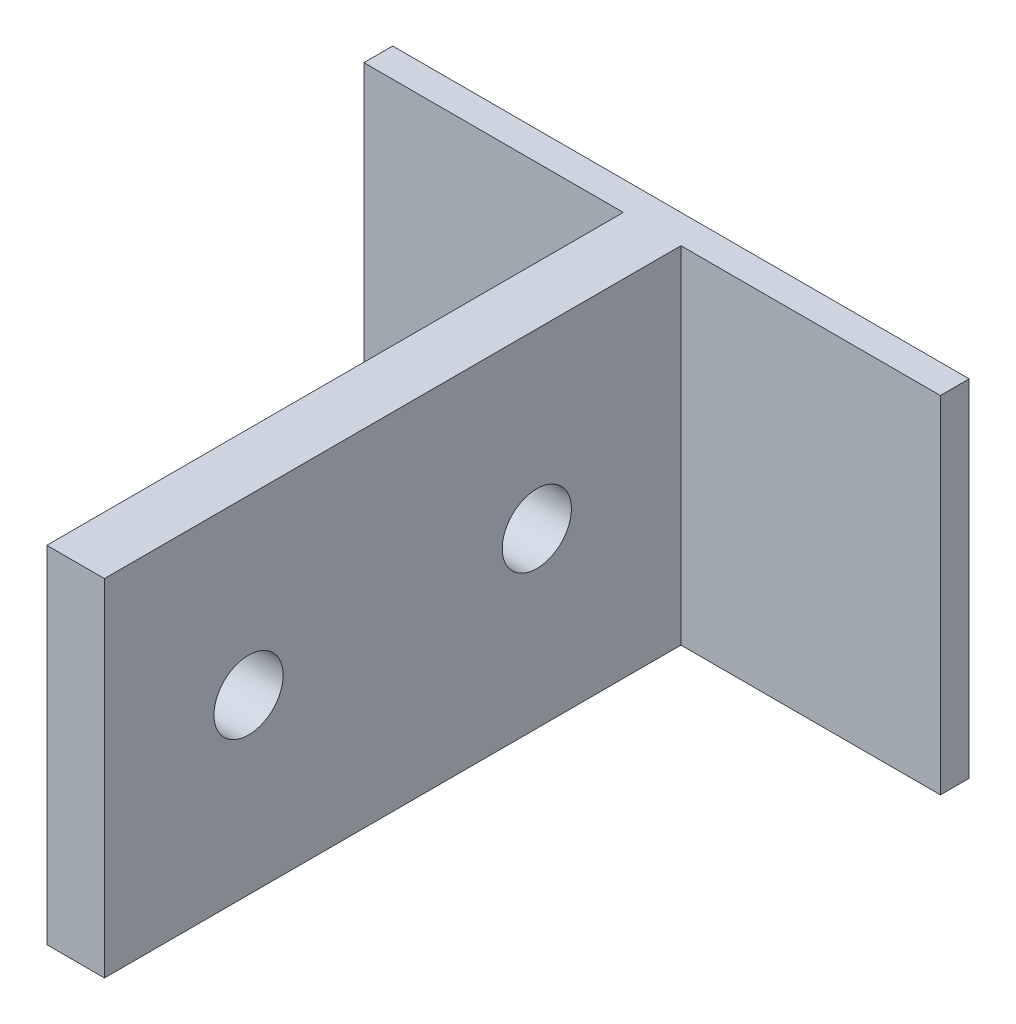
SolidWorks part; units mm, degrees
material "AISI 1020"
ref_plane "Alzado" through (0, 0, 0) normal (0, 0, 1) x (1, 0, 0)
ref_plane "Planta" through (0, 0, 0) normal (0, 1, 0) x (1, 0, 0)
ref_plane "Vista lateral" through (0, 0, 0) normal (1, 0, 0) x (0, 0, -1)
sketch "Croquis3" plane through (0, 0, 0) normal (0, 0, 1) x (1, 0, 0)
  line L1 (-50, -30) -> (50, -30)
  line L2 (-50, -30) -> (-50, 30)
  line L3 (-50, 30) -> (50, 30)
  line L4 (50, -30) -> (50, 30)
  line L9 (-5, 30) -> (5, 30)
  line L10 (-5, 30) -> (-5, -30)
  line L11 (-5, -30) -> (5, -30)
  line L12 (5, 30) -> (5, -30)
  point P6 (0, -30)
  point P7 (0, 30)
  point P8 (-50, 0)
  point P9 (50, 0)
  point P13 (0, -30)
  point P14 (0, 30)
  dimension "D1" = 100
  dimension "D2" = 60
  dimension "D3" = 10
extrude "Saliente-Extruir1" add sketch "Croquis3" against normal blind 5 contours L4 L3 L2 L1
extrude "Saliente-Extruir2" add sketch "Croquis3<3>" along normal blind 100 contours L12 L3 L10 L1 region at (0, 0, 0)
sketch "Croquis3<3>" plane through (0, 0, 0) normal (0, 0, 1) x (1, 0, 0) same geometry as "Croquis3"
sketch "Croquis5" plane through (5, 0, 0) normal (1, 0, 0) x (0, 0, -1)
  line L1 (-100, 30) -> (-100, -30) construction
  line L6 (0, -30) -> (0, 30) construction
  line L7 (-100, 30) -> (0, 30) construction
  circle A0 centre (-75, 0) radius 6
  circle A1 centre (-25, 0) radius 6
  dimension "D1" = 12
  dimension "D3" = 12
  dimension "D2" = 25
  dimension "D4" = 25
  dimension "D5" = 30
  dimension "D6" = 30
extrude "Cortar-Extruir1" cut sketch "Croquis5" against normal blind 20 contours A0 | A1
